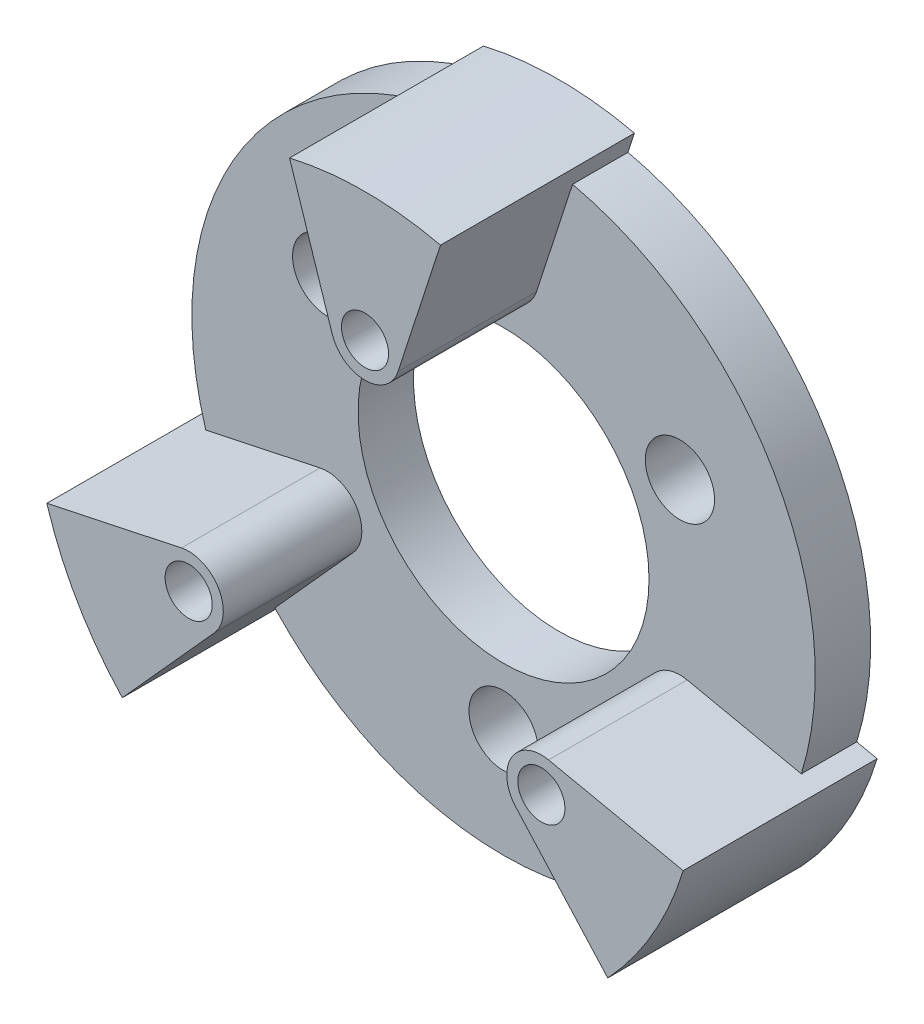
SolidWorks part; units mm, degrees
ref_plane "Front Plane" through (0, 0, 0) normal (0, 0, 1) x (1, 0, 0)
ref_plane "Top Plane" through (0, 0, 0) normal (0, 1, 0) x (1, 0, 0)
ref_plane "Right Plane" through (0, 0, 0) normal (1, 0, 0) x (0, 0, -1)
sketch "Sketch1" plane through (0, 0, 0) normal (0, 0, 1) x (1, 0, 0)
  line L0 (0, 0) -> (28.6934, -16.5661) construction
  line L1 (0, 0) -> (-25.9032, -14.9552) construction
  line L2 (0, 0) -> (0, 25.9112) construction
  circle A0 centre (0, 0) radius 10.5
  circle A1 centre (0, 0) radius 14.7 construction
  circle A2 centre (0, 0) radius 4.2 construction
  circle A3 centre (12.7306, -7.35) radius 10.5 construction
  circle A5 centre (-12.7306, -7.35) radius 10.5 construction
  circle A6 centre (12.7306, -7.35) radius 1.5
  circle A7 centre (0, 14.7) radius 1.5
  circle A8 centre (-12.7306, -7.35) radius 1.5
  circle A9 centre (0, 0) radius 22.5
  dimension "D1" = 21
  dimension "D2" = 8.4
  dimension "D3" = 21
  dimension "D4" = 120
  dimension "D6" = 3
  dimension "D7" = 45
  dimension "D5" = 120
extrude "Boss-Extrude1" add sketch "Sketch1" along normal blind 4 contours A9 A0 | A0 A9 | A0 A9 | A0 A8 | A0 A6 | A0 A7 region at (-21.8636, 0, 0)
sketch "Sketch4" plane through (0, 0, 4) normal (0, 0, 1) x (1, 0, 0)
  line L0 (-10.8727, -9.0228) -> (-17.5188, -16.404)
  line L1 (-13.2504, -4.9046) -> (-22.9657, -6.9697)
  line L2 (-12.7306, -7.35) -> (0, 0) construction
  line L7 (0, 0) -> (0, -14.7) construction
  line L9 (2.3776, 13.9275) -> (5.4469, 23.3737)
  line L10 (-2.3776, 13.9275) -> (-5.4469, 23.3737)
  line L11 (10.8727, -9.0228) -> (17.5188, -16.404)
  line L12 (13.2504, -4.9046) -> (22.9657, -6.9697)
  circle A9 centre (-12.7306, -7.35) radius 1.5
  circle A24 centre (0, -14.7) radius 2.5
  circle A28 centre (0, 0) radius 22.5 construction
  circle A29 centre (-12.7306, 7.35) radius 2.5
  circle A30 centre (12.7306, 7.35) radius 2.5
  arc A31 (-22.9657, -6.9697) -> (-17.5188, -16.404) centre (0, 0) ccw
  arc A32 (-10.8727, -9.0228) -> (-13.2504, -4.9046) centre (-12.7306, -7.35) ccw
  circle A37 centre (0, 0) radius 24 construction
  arc A40 (5.4469, 23.3737) -> (-5.4469, 23.3737) centre (0, 0) ccw
  arc A41 (-2.3776, 13.9275) -> (2.3776, 13.9275) centre (0, 14.7) ccw
  arc A42 (17.5188, -16.404) -> (22.9657, -6.9697) centre (0, 0) ccw
  arc A43 (13.2504, -4.9046) -> (10.8727, -9.0228) centre (12.7306, -7.35) ccw
  circle A44 centre (0, 14.7) radius 1.5
  circle A45 centre (12.7306, -7.35) radius 1.5
  circle M10 centre (0, 0) radius 22.5
  circle M12 centre (12.7306, -7.35) radius 1.5
  circle M13 centre (0, 14.7) radius 1.5
  circle M14 centre (-12.7306, -7.35) radius 1.5
  dimension "D1" = 3
  dimension "D2" = 5
  dimension "D3" = 3
  dimension "D4" = 5
  dimension "D5" = 3
  dimension "D6" = 3
  dimension "D9" = 1.5
  dimension "D10" = 45
  dimension "D7" = 18
  dimension "D8" = 18
extrude "Boss-Extrude4" add sketch "Sketch4" against normal up to surface (4 mm away) up to face at (10.5, 0, 0)
extrude "Boss-Extrude5" add sketch "Sketch4<5>" along normal blind 10 contours L9 A40 L10 M10 | L10 A41 L9 M10 M13 | L1 A31 L0 M10 | L0 A32 L1 M10 M14 | L12 A43 L11 M10 M12 | L11 A42 L12 M10 region at (-16.0662, -9.2758, 4) region at (-19.9734, -11.5316, 4) region at (19.9734, -11.5316, 4) region at (16.0662, -9.2758, 4) region at (0, 18.5517, 4) region at (0, 23.0633, 4)
sketch "Sketch4<5>" plane through (0, 0, 4) normal (0, 0, 1) x (1, 0, 0) same geometry as "Sketch4"
extrude "Cut-Extrude1" cut sketch "Sketch4<3>" against normal through all both and the other way through all contours A24 | A29 | A30 region at (0, -14.7, 4) region at (-12.7306, 7.35, 4) region at (12.7306, 7.35, 4)
sketch "Sketch4<3>" plane through (0, 0, 4) normal (0, 0, 1) x (1, 0, 0) same geometry as "Sketch4"
hole_wizard "CSK for M3 Flat Head Machine Screw1" positions "Sketch5" profile "Sketch6" countersink size "M3" standard "ANSI Metric" end condition through all
sketch "Sketch5" plane through (0, 0, 0) normal (0, 0, -1) x (-1, 0, 0)
  point P0 (12.7306, -7.35)
  point P3 (0, 14.7)
  point P6 (-12.7306, -7.35)
sketch "Sketch6" plane through (-12.7306, -7.35, 0) normal (1, 0, 0) x (0, 1, 0)
  line L0 (0, 0) -> (0, 14)
  line L1 (0, 14) -> (1.7, 14)
  line L2 (1.7, 14) -> (1.7, 1.45)
  line L3 (1.7, 1.45) -> (3.15, 0)
  line L5 (3.15, 0) -> (0, 0)
  line L6 (-1.7, 1.45) -> (-3.15, 0) construction
  line L11 (0, -6.35) -> (0, 107.95) construction
  dimension "Thru Hole Dia." = 3.4
  dimension "Thru Hole Depth" = 14
  dimension "Near C'Sink Dia." = 6.3
  dimension "Near C'Sink Angle" = 90
